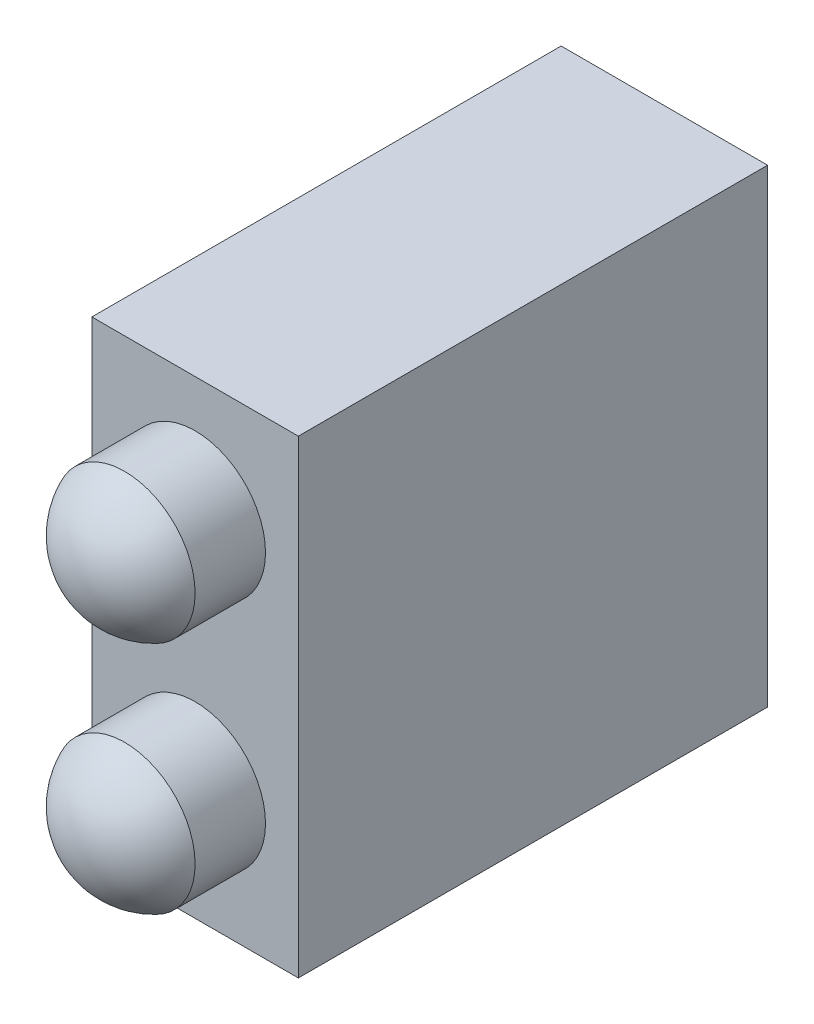
SolidWorks part; units mm, degrees
material "ABS"
ref_plane "Front Plane" through (0, 0, 0) normal (0, 0, 1) x (1, 0, 0)
ref_plane "Top Plane" through (0, 0, 0) normal (0, 1, 0) x (1, 0, 0)
ref_plane "Right Plane" through (0, 0, 0) normal (1, 0, 0) x (0, 0, -1)
sketch "Sketch1" plane through (0, 0, 0) normal (0, 0, 1) x (1, 0, 0)
  line L1 (-2.2, 5) -> (2.2, 5)
  line L2 (-2.2, 5) -> (-2.2, -5)
  line L3 (-2.2, -5) -> (2.2, -5)
  line L4 (2.2, 5) -> (2.2, -5)
  line L5 (-2.2, 5) -> (2.2, -5) construction
  line L6 (-2.2, -5) -> (2.2, 5) construction
  point P0 (0, 0)
  dimension "D1" = 10
  dimension "D2" = 4.4
extrude "Boss-Extrude1" add sketch "Sketch1" against normal blind 10
sketch "Sketch2" plane through (0, 0, 0) normal (0, 0, 1) x (1, 0, 0)
  line L0 (0, 0) -> (0, 2.5) construction
  circle A0 centre (0, 2.5) radius 1.5
  dimension "D1" = 3
  dimension "D2" = 2.5
extrude "Boss-Extrude2" add sketch "Sketch2" along normal blind 1.5
dome "Dome1" faces to dome 1 distance 1 reverse direction no elliptical dome no face at (1.5, 2.5, 1.5) parameters "D1"=1
mirror "Mirror1" about plane through (0, 0, 0) normal (0, 1, 0) of "Dome1", "Boss-Extrude2"
